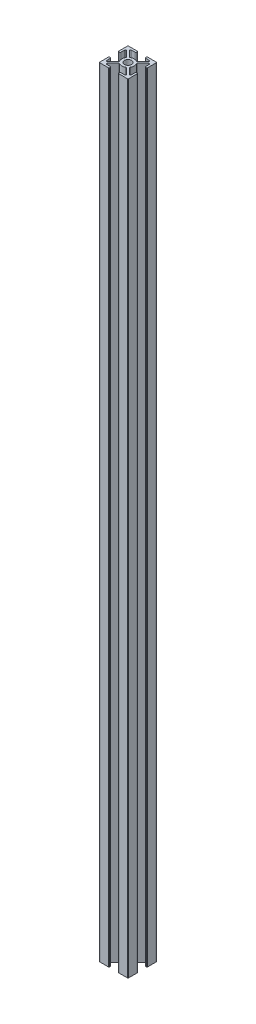
SolidWorks part; units mm, degrees
ref_plane "Front Plane" through (0, 0, 0) normal (0, 0, 1) x (1, 0, 0)
ref_plane "Top Plane" through (0, 0, 0) normal (0, 1, 0) x (1, 0, 0)
ref_plane "Right Plane" through (0, 0, 0) normal (1, 0, 0) x (0, 0, -1)
sketch "Sketch1" plane through (0, 0, 0) normal (0, 1, 0) x (1, 0, 0)
  line L26 (-8.6, 8.6) -> (8.6, 8.6) construction
  line L27 (-8.6, -8.6) -> (-8.6, 8.6) construction
  line L28 (8.6, -8.6) -> (8.6, 8.6) construction
  line L29 (-8.6, -8.6) -> (8.6, -8.6) construction
  line L57 (-10, -10) -> (-10, 10) construction
  line L59 (10, -10) -> (10, 10) construction
  line L63 (-10, -10) -> (10, -10) construction
  line L64 (-10, 10) -> (10, 10) construction
  point P157 (-15.6267, -3.3945)
  point P158 (-2.4692, 3.4591)
  line B0 (-6.2474, 8.6) -> (-3.6, 8.6)
  line B1 (-9.5, -10) -> (-3.6, -10)
  line B2 (-10, -9.5) -> (-10, -3.6)
  line B3 (-9.5, 10) -> (-3.6, 10)
  line B4 (10, -9.5) -> (10, -3.6)
  line B5 (-10, -10) -> (10, 10) construction
  line B6 (-10, 10) -> (10, -10) construction
  line B7 (8.6, -6.2474) -> (8.6, -3.6)
  line B8 (-6.2474, -8.6) -> (-3.6, -8.6)
  line B9 (-8.6, -6.2474) -> (-8.6, -3.6)
  line B10 (-7.7464, 6.7565) -> (-3.7448, 2.7548)
  line B11 (-6.6465, 7.6365) -> (-2.7548, 3.7448)
  line B12 (6.6465, 7.6365) -> (2.7548, 3.7448)
  line B13 (7.6365, 6.6465) -> (3.7448, 2.7548)
  line B14 (7.6365, -6.6465) -> (3.7448, -2.7548)
  line B15 (6.6465, -7.6365) -> (2.7548, -3.7448)
  line B16 (-6.6465, -7.6365) -> (-2.7548, -3.7448)
  line B17 (-7.6365, -6.6465) -> (-3.7448, -2.7548)
  line B18 (-3.4591, 2.4692) -> (-8.6, 7.6101) construction
  line B19 (-2.4692, 3.4591) -> (-7.6101, 8.6) construction
  line B20 (3.4591, -2.4692) -> (8.6, -7.6101) construction
  line B21 (2.4692, -3.4591) -> (7.6101, -8.6) construction
  line B22 (-2.4692, -3.4591) -> (-7.6101, -8.6) construction
  line B23 (3.4591, 2.4692) -> (8.6, 7.6101) construction
  line B24 (-3.4591, -2.4692) -> (-8.6, -7.6101) construction
  line B25 (2.4692, 3.4591) -> (7.6101, 8.6) construction
  line B26 (-8.6, 6.4029) -> (-8.6, 3.6)
  line B27 (-7.6101, 8.6) -> (-3.2, 8.6) construction
  line B28 (8.6, -7.6101) -> (8.6, -3.2) construction
  line B29 (6.2474, -8.6) -> (3.6, -8.6)
  line B30 (-9, 3.2) -> (-9.6, 3.2)
  line B31 (-10, -3.2) -> (10, -3.2) construction
  line B32 (-10, 3.2) -> (10, 3.2) construction
  line B33 (-10, -3.2) -> (10, 3.2) construction
  line B34 (-10, 3.2) -> (10, -3.2) construction
  line B35 (-9.6, -3.2) -> (-9, -3.2)
  line B36 (9, 3.2) -> (9.6, 3.2)
  line B37 (9, -3.2) -> (9.6, -3.2)
  line B38 (-8.6, 3.2) -> (-8.6, 7.6101) construction
  line B39 (-8.6, -3.2) -> (-8.6, -7.6101) construction
  line B40 (-10, 3.6) -> (-10, 9.5)
  line B41 (10, 3.6) -> (10, 9.5)
  line B42 (8.6, 3.6) -> (8.6, 6.2474)
  line B43 (8.6, 7.6101) -> (8.6, 3.2) construction
  line B44 (-3.2, 9.6) -> (-3.2, 9)
  line B45 (-3.2, -10) -> (-3.2, 10) construction
  line B46 (3.2, -10) -> (3.2, 10) construction
  line B47 (-3.2, -10) -> (3.2, 10) construction
  line B48 (-3.2, 10) -> (3.2, -10) construction
  line B49 (3.2, 9.6) -> (3.2, 9)
  line B50 (-3.2, -9.6) -> (-3.2, -9)
  line B51 (3.2, -9.6) -> (3.2, -9)
  line B52 (3.6, -10) -> (9.5, -10)
  line B53 (3.2, -8.6) -> (7.6101, -8.6) construction
  line B54 (-3.2, -8.6) -> (-7.6101, -8.6) construction
  line B55 (3.6, 10) -> (9.5, 10)
  line B56 (3.6, 8.6) -> (6.2474, 8.6)
  line B57 (3.2, 8.6) -> (7.6101, 8.6) construction
  circle B58 centre (0, 0) radius 2.5
  arc B59 (-3.6669, 2.1485) -> (-3.6669, -2.1485) centre (0, 0) ccw
  arc B60 (2.1485, 3.6669) -> (-2.1485, 3.6669) centre (0, 0) ccw
  arc B61 (3.6669, -2.1485) -> (3.6669, 2.1485) centre (0, 0) ccw
  arc B62 (-2.1485, -3.6669) -> (2.1485, -3.6669) centre (0, 0) ccw
  arc B63 (-10, -9.5) -> (-9.5, -10) centre (-9.5, -9.5) ccw
  arc B64 (9.5, -10) -> (10, -9.5) centre (9.5, -9.5) ccw
  arc B65 (10, 9.5) -> (9.5, 10) centre (9.5, 9.5) ccw
  arc B66 (-9.5, 10) -> (-10, 9.5) centre (-9.5, 9.5) ccw
  arc B67 (-7.7464, 6.7565) -> (-8.6, 6.4029) centre (-8.1, 6.4029) ccw
  arc B68 (-6.2474, -8.6) -> (-6.6465, -7.6365) centre (-6.2474, -8.0356) cw
  arc B69 (-8.6, -6.2474) -> (-7.6365, -6.6465) centre (-8.0356, -6.2474) ccw
  arc B70 (6.2474, -8.6) -> (6.6465, -7.6365) centre (6.2474, -8.0356) ccw
  arc B71 (7.6365, -6.6465) -> (8.6, -6.2474) centre (8.0356, -6.2474) ccw
  arc B72 (8.6, 6.2474) -> (7.6365, 6.6465) centre (8.0356, 6.2474) ccw
  arc B73 (6.6465, 7.6365) -> (6.2474, 8.6) centre (6.2474, 8.0356) ccw
  arc B74 (-6.2474, 8.6) -> (-6.6465, 7.6365) centre (-6.2474, 8.0356) ccw
  arc B75 (2.7548, 3.7448) -> (2.1485, 3.6669) centre (2.4013, 4.0983) cw
  arc B76 (3.7448, 2.7548) -> (3.6669, 2.1485) centre (4.0983, 2.4013) ccw
  arc B77 (3.7448, -2.7548) -> (3.6669, -2.1485) centre (4.0983, -2.4013) cw
  arc B78 (2.7548, -3.7448) -> (2.1485, -3.6669) centre (2.4013, -4.0983) ccw
  arc B79 (-2.1485, -3.6669) -> (-2.7548, -3.7448) centre (-2.4013, -4.0983) ccw
  arc B80 (-3.7448, -2.7548) -> (-3.6669, -2.1485) centre (-4.0983, -2.4013) ccw
  arc B81 (-3.7448, 2.7548) -> (-3.6669, 2.1485) centre (-4.0983, 2.4013) cw
  arc B82 (-2.1485, 3.6669) -> (-2.7548, 3.7448) centre (-2.4013, 4.0983) cw
  arc B83 (-3.2, 9) -> (-3.6, 8.6) centre (-3.6, 9) cw
  arc B84 (-3.2, 9.6) -> (-3.6, 10) centre (-3.6, 9.6) ccw
  arc B85 (3.2, 9.6) -> (3.6, 10) centre (3.6, 9.6) cw
  arc B86 (3.2, 9) -> (3.6, 8.6) centre (3.6, 9) ccw
  arc B87 (9.6, 3.2) -> (10, 3.6) centre (9.6, 3.6) ccw
  arc B88 (9, 3.2) -> (8.6, 3.6) centre (9, 3.6) cw
  arc B89 (9.6, -3.2) -> (10, -3.6) centre (9.6, -3.6) cw
  arc B90 (9, -3.2) -> (8.6, -3.6) centre (9, -3.6) ccw
  arc B91 (3.2, -9) -> (3.6, -8.6) centre (3.6, -9) cw
  arc B92 (3.2, -9.6) -> (3.6, -10) centre (3.6, -9.6) ccw
  arc B93 (-3.2, -9.6) -> (-3.6, -10) centre (-3.6, -9.6) cw
  arc B94 (-3.2, -9) -> (-3.6, -8.6) centre (-3.6, -9) ccw
  arc B95 (-9, -3.2) -> (-8.6, -3.6) centre (-9, -3.6) cw
  arc B96 (-9.6, -3.2) -> (-10, -3.6) centre (-9.6, -3.6) ccw
  arc B97 (-9, 3.2) -> (-8.6, 3.6) centre (-9, 3.6) ccw
  arc B98 (-9.6, 3.2) -> (-10, 3.6) centre (-9.6, 3.6) cw
sketch_block_instance "Block3-1"
sketch_block "Block3" parameters "D4"=2.5, "D5"=4.25, "D10"=0.5, "D12"=0.5, "D13"=0.5644, "D14"=0.5, "D15"=0.4, "D1"=20, "D2"=1.4, "D3"=1.4, "D6"=6.4, "D7"=0.7, "D8"=1.4, "D9"=20, "D11"=6.4, "D16"=1.4
extrude "Boss-Extrude1" add sketch "Sketch1" along normal blind 540
